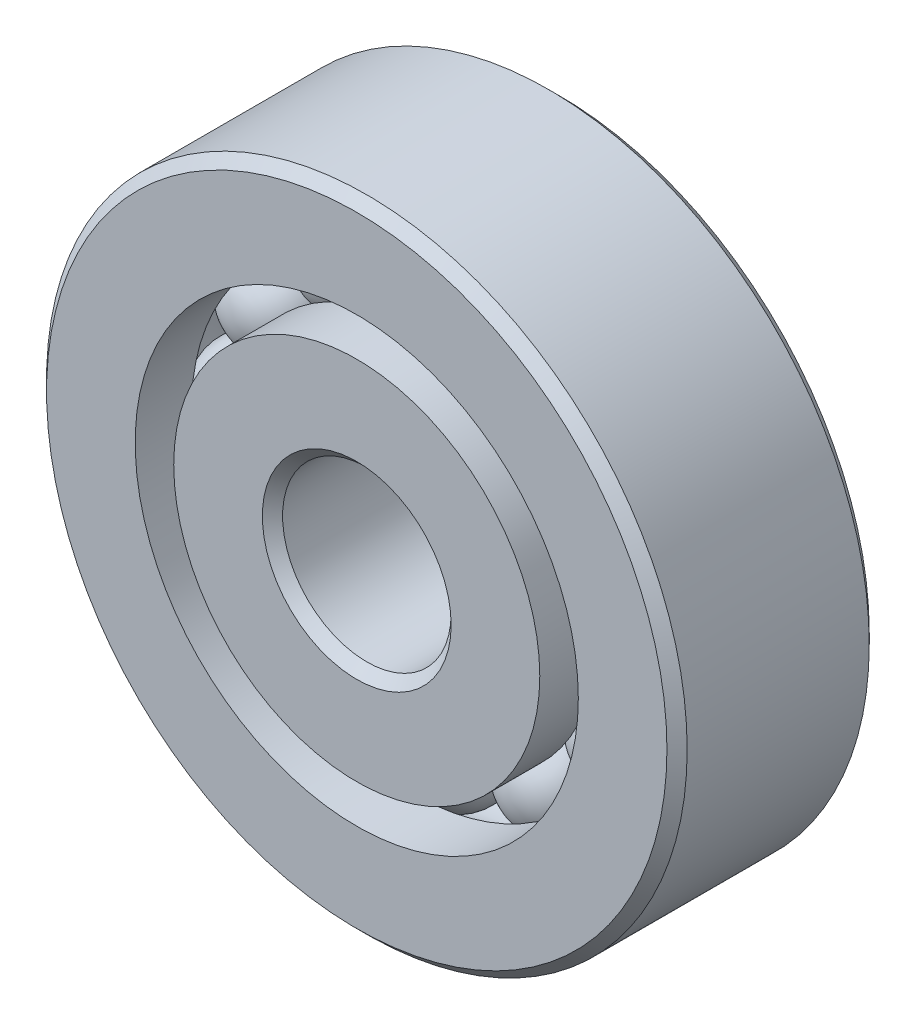
SolidWorks part; units mm, degrees
ref_plane "Front Plane" through (0, 0, 0) normal (0, 0, 1) x (1, 0, 0)
ref_plane "Top Plane" through (0, 0, 0) normal (0, 1, 0) x (1, 0, 0)
ref_plane "Right Plane" through (0, 0, 0) normal (1, 0, 0) x (0, 0, -1)
sketch "Sketch1" plane through (0, 0, 0) normal (1, 0, 0) x (0, 0, -1)
  line L0 (-3, 0) -> (3, 0) construction
  line L1 (0, 9.5) -> (0, -9.5) construction
  line L2 (2.7, 9.5) -> (-2.7, 9.5)
  line L3 (-2.7, 9.5) -> (-3, 9.2)
  line L4 (-3, 9.2) -> (-3, 6.5714)
  line L5 (-3, 6.5714) -> (-1.3333, 6.5714)
  line L6 (3, 6.5714) -> (1.3333, 6.5714)
  line L7 (3, 9.2) -> (3, 6.5714)
  line L8 (2.7, 9.5) -> (3, 9.2)
  line L9 (0, 9.5) -> (0, 6) construction
  line L10 (0, 6) -> (0, 2.5) construction
  arc A0 (-1.3333, 6.5714) -> (1.3333, 6.5714) centre (0, 6) cw
  point P14 (0, 2.5)
  dimension "Width" = 6
  dimension "OD" = 19
  dimension "D1" = 45
  dimension "D2" = 0.3
  dimension "Shaft Dia" = 5
  dimension "D3" = 2.6667
  dimension "D4" = 0.5714
revolve "Revolve1" add sketch "Sketch1" angle 360 about L0
sketch "Sketch3" plane through (0, 0, 0) normal (1, 0, 0) x (0, 0, -1)
  line L0 (-3, 5.4286) -> (-1.3333, 5.4286)
  line L1 (0, 9.5) -> (0, -9.5) construction
  line L2 (-3, 9.2) -> (-3, 6.5714) construction
  line L3 (-3, 5.4286) -> (-3, 2.8)
  line L4 (-2.7, 9.5) -> (-3, 9.2) construction
  line L5 (-3, 2.8) -> (-2.7, 2.5)
  line L6 (-2.7, 2.5) -> (2.7, 2.5)
  line L7 (2.7, 9.5) -> (2.7, -9.5) construction
  line L8 (2.7, 2.5) -> (3, 2.8)
  line L9 (3, -9.2) -> (3, 9.2) construction
  line L10 (3, 2.8) -> (3, 5.4286)
  line L11 (3, 5.4286) -> (1.3333, 5.4286)
  line L13 (2.7, 9.5) -> (3, 9.2) construction
  arc A0 (1.3333, 6.5714) -> (-1.3333, 6.5714) centre (0, 6) ccw construction
  arc A1 (1.3333, 5.4286) -> (-1.3333, 5.4286) centre (0, 6) cw
revolve "Revolve3" add sketch "Sketch3" angle 360 about L0
sketch "Sketch4" plane through (0, 0, 0) normal (1, 0, 0) x (0, 0, -1)
  line L0 (-1.4506, 6) -> (1.4506, 6)
  arc A2 (-1.4506, 6) -> (1.4506, 6) centre (0, 6) cw
  arc A3 (1.3333, 6.5714) -> (-1.3333, 6.5714) centre (0, 6) ccw construction
revolve "Revolve4" add sketch "Sketch4" angle 360 about L0
ref_axis "Axis1" through (0, 0, -3) along (0, 0, 1)
pattern_circular "CirPattern1" count 12 every 30 about axis through (0, 0, -3) along (0, 0, 1) of bodies 104
sketch "Sketch5" plane through (0, 0, 0) normal (1, 0, 0) x (0, 0, -1)
  line L0 (-3, 6.5714) -> (-1.3333, 6.5714) construction
  line L1 (-2.85, 6.5714) -> (-1.4506, 6.5714)
  line L2 (-2.85, 6.5714) -> (-2.85, 5.4286)
  line L3 (-2.85, 5.4286) -> (-1.4506, 5.4286)
  line L4 (-1.4506, 6.5714) -> (-1.4506, 5.4286)
  line L5 (-3, 5.4286) -> (-1.3333, 5.4286) construction
  line L6 (3, 6.5714) -> (1.3333, 6.5714) construction
  line L7 (2.85, 6.5714) -> (1.4506, 6.5714)
  line L8 (2.85, 6.5714) -> (2.85, 5.4286)
  line L9 (2.85, 5.4286) -> (1.4506, 5.4286)
  line L10 (1.4506, 6.5714) -> (1.4506, 5.4286)
  line L11 (3, 5.4286) -> (1.3333, 5.4286) construction
  line L12 (-2.7, 9.5) -> (-3, 9.2) construction
  point P18 (-2.85, 9.35)
equation "\"D2@Sketch1\" = \"Width@Sketch1\"*.05"
equation "\"D3@Sketch1\" = \"Width@Sketch1\"/2.25"
equation "\"D4@Sketch1\" = (((\"OD@Sketch1\"-\"Width@Sketch1\")/2)/3.25)/3.5"
equation "\"D2@CirPattern1\" = 360/\"Balls@CirPattern1\""
